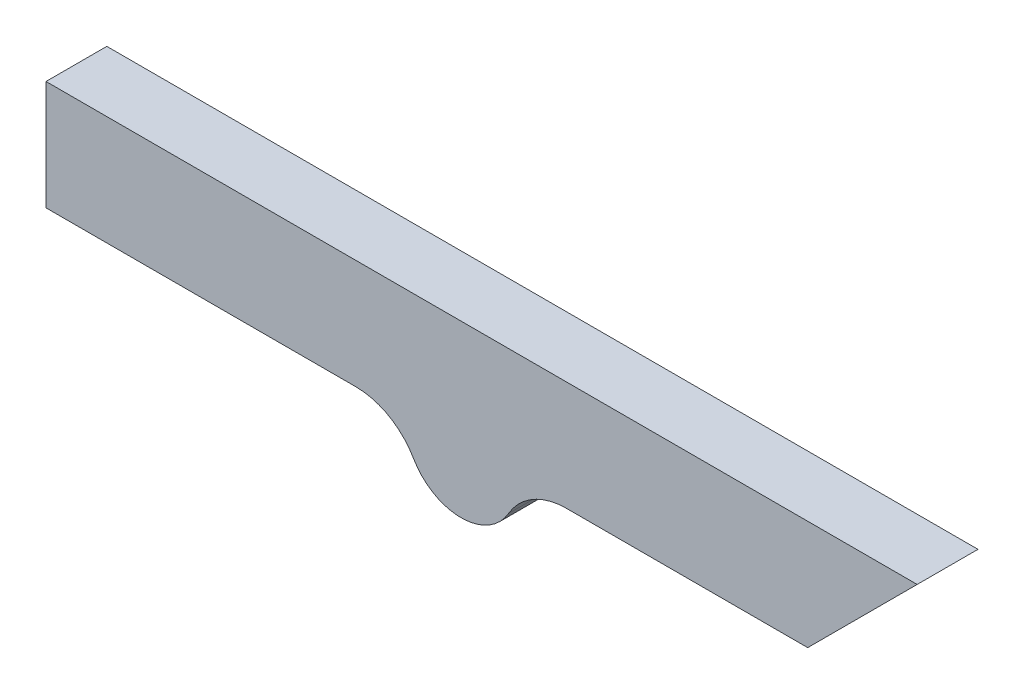
SolidWorks part; units mm, degrees
ref_plane "Front Plane" through (0, 0, 0) normal (0, 0, 1) x (1, 0, 0)
ref_plane "Top Plane" through (0, 0, 0) normal (0, 1, 0) x (1, 0, 0)
ref_plane "Right Plane" through (0, 0, 0) normal (1, 0, 0) x (0, 0, -1)
sketch "Sketch1" plane through (0, 0, 0) normal (0, 0, 1) x (1, 0, 0)
  line L0 (22.9331, 13.175) -> (11.75, 13.175)
  line L1 (11.75, 13.175) -> (11.75, 11.375)
  line L2 (11.75, 11.375) -> (13.8429, 11.375)
  line L3 (17.3071, 11.375) -> (21.1331, 11.375)
  line L4 (21.1331, 11.375) -> (22.9331, 13.175)
  line L5 (21.1745, 11.275) -> (23.1745, 13.275)
  line L6 (23.1745, 13.275) -> (11.65, 13.275)
  line L7 (11.65, 13.275) -> (11.65, 11.275)
  line L8 (11.65, 11.275) -> (13.8429, 11.275)
  line L9 (17.3071, 11.275) -> (21.1745, 11.275)
  line L10 (21.1745, 11.275) -> (23.1745, 13.275)
  line L11 (23.1745, 13.275) -> (11.65, 13.275)
  line L12 (11.65, 13.275) -> (11.65, 11.275)
  line L13 (11.65, 11.275) -> (13.8429, 11.275)
  line L14 (17.3071, 11.275) -> (21.1745, 11.275)
  line L15 (22.9331, 13.175) -> (23.0745, 13.175)
  line L16 (11.75, 13.175) -> (8.75, 13.175)
  line L17 (11.75, 13.175) -> (11.75, 11.375)
  line L18 (11.75, 11.375) -> (8.75, 11.375)
  line L19 (21.1331, 11.375) -> (21.2745, 11.375)
  line L29 (8.75, 13.175) -> (8.75, 11.375)
  arc A0 (14.7956, 10.825) -> (13.8429, 11.375) centre (13.8429, 10.275) ccw
  arc A1 (14.7956, 10.825) -> (16.3544, 10.825) centre (15.575, 11.275) ccw
  arc A2 (17.3071, 11.375) -> (16.3544, 10.825) centre (17.3071, 10.275) ccw
  arc A7 (14.709, 10.775) -> (13.8429, 11.275) centre (13.8429, 10.275) ccw
  arc A8 (14.709, 10.775) -> (16.441, 10.775) centre (15.575, 11.275) ccw
  arc A9 (17.3071, 11.275) -> (16.441, 10.775) centre (17.3071, 10.275) ccw
  arc A10 (14.709, 10.775) -> (13.8429, 11.275) centre (13.8429, 10.275) ccw
  arc A11 (14.709, 10.775) -> (16.441, 10.775) centre (15.575, 11.275) ccw
  arc A12 (17.3071, 11.275) -> (16.441, 10.775) centre (17.3071, 10.275) ccw
  point P24 (0, 0)
  point P27 (0, 0)
  dimension "D3" = 3
  dimension "D1" = 0
  dimension "D2" = 0.1
extrude "Shape" add sketch "Sketch1" along normal blind 1 contours A2 L3 L4 L0 L1 L2 A0 A1 | L4 L19 L10 L15 | L18 L1 L16 L12 | L16 L29 L18 L12 region at (16.7953, 12.1929, 0) region at (22.1038, 12.275, 0) region at (11.7, 12.275, 0) region at (10.2, 12.275, 0)
